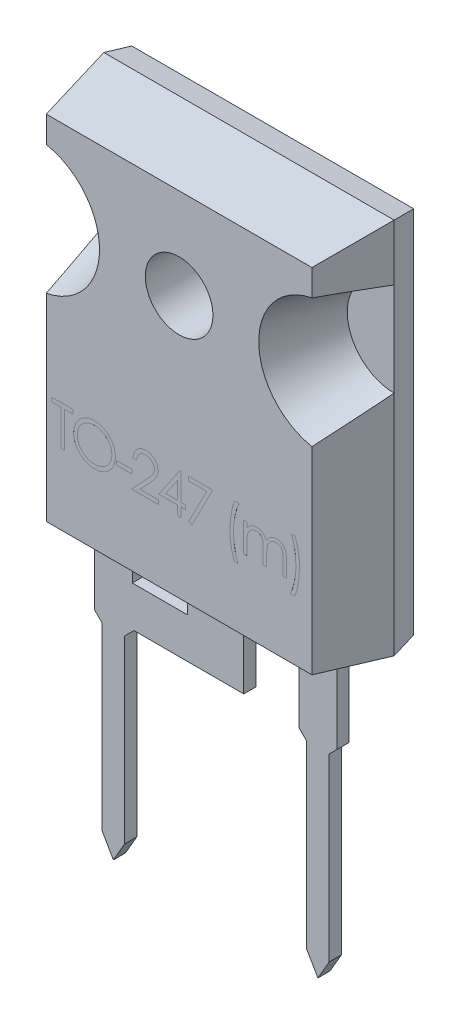
SolidWorks part; units mm, degrees
ref_plane "Front Plane" through (0, 0, 0) normal (0, 0, 1) x (1, 0, 0)
ref_plane "Top Plane" through (0, 0, 0) normal (0, 1, 0) x (1, 0, 0)
ref_plane "Right Plane" through (0, 0, 0) normal (1, 0, 0) x (0, 0, -1)
sketch "Sketch1" plane through (0, 0, 0) normal (0, 0, 1) x (1, 0, 0)
  line L1 (-7.75, 10.075) -> (7.75, 10.075)
  line L2 (-7.75, 10.075) -> (-7.75, -10.075)
  line L3 (-7.75, -10.075) -> (7.75, -10.075)
  line L4 (7.75, 10.075) -> (7.75, -10.075)
  line L5 (-7.75, 10.075) -> (7.75, -10.075) construction
  line L6 (-7.75, -10.075) -> (7.75, 10.075) construction
  point P0 (0, 0)
  dimension "D1" = 15.5
  dimension "D2" = 20.15
extrude "Boss-Extrude1" add sketch "Sketch1" against normal blind 1.27 draft 10 and the other way blind 3.73 draft 10
sketch "Sketch2" plane through (0, 0, 0) normal (0, 0, 1) x (1, 0, 0)
  line L0 (7.75, 10.075) -> (-7.75, 10.075) construction
  line L1 (-5.25, 7.4139) -> (-5.25, 0.8413) construction
  line L2 (-7.75, 10.075) -> (-7.75, -10.075) construction
  line L3 (0, 14.1994) -> (0, -3.2617) construction
  line L4 (7.75, -10.075) -> (7.75, 10.075) construction
  circle A0 centre (0, 4.565) radius 1.805 construction
  circle A1 centre (-7.75, 4.575) radius 2.5
  circle A2 centre (7.75, 4.575) radius 2.5
  dimension "D1" = 5.51
  dimension "D2" = 3.61
  dimension "D3" = 5.5
  dimension "D4" = 5
  dimension "D5" = 2.5
  dimension "D6" = 7.75
extrude "Cut-Extrude1" cut sketch "Sketch2" along normal up to surface (3.73 mm away) draft 15
sketch "Sketch4" plane through (0, 0, 0) normal (0, 0, 1) x (1, 0, 0)
  line L0 (7.75, 10.075) -> (-7.75, 10.075) construction
  circle A0 centre (0, 4.565) radius 1.805
  dimension "D1" = 3.61
  dimension "D2" = 5.51
extrude "Cut-Extrude2" cut sketch "Sketch4" along normal through all both and the other way through all
sketch "Sketch5" plane through (0, 0, 0) normal (0, 1, 0) x (1, 0, 0)
  line L0 (-9.5483, -1.13) -> (8.845, -1.13) construction
  line L1 (7.5261, 1.27) -> (-7.5261, 1.27) construction
  line L2 (0, 2.9425) -> (0, -4.6836) construction
  line L3 (-6.47, -1.13) -> (-4.45, -1.13)
  line L4 (-6.47, -1.13) -> (-6.47, -1.78)
  line L5 (-6.47, -1.78) -> (-4.45, -1.78)
  line L6 (-4.45, -1.13) -> (-4.45, -1.78)
  line L7 (-5.46, -1.13) -> (-5.46, -1.78) construction
  line L8 (6.47, -1.13) -> (6.47, -1.78)
  line L9 (6.47, -1.13) -> (4.45, -1.13)
  line L10 (4.45, -1.13) -> (4.45, -1.78)
  line L11 (6.47, -1.78) -> (4.45, -1.78)
  line L13 (-1.5, -1.13) -> (1.5, -1.13)
  line L14 (-1.5, -1.13) -> (-1.5, -1.78)
  line L15 (-1.5, -1.78) -> (1.5, -1.78)
  line L16 (1.5, -1.13) -> (1.5, -1.78)
  point P21 (0, -1.13)
  dimension "D1" = 2.4
  dimension "D2" = 2.02
  dimension "D3" = 0.65
  dimension "D4" = 5.46
  dimension "D5" = 3
extrude "Boss-Extrude2" add sketch "Sketch5" against normal blind 14.07
sketch "Sketch6" plane through (0, 0, 1.78) normal (0, 0, 1) x (1, 0, 0)
  line L0 (1.5, -14.07) -> (-6.47, -14.07)
  line L1 (-6.47, -14.07) -> (-6.47, -11.9156)
  line L2 (-6.47, -14.07) -> (-6.47, -9.7611) construction
  line L3 (-6.47, -11.9156) -> (1.5, -11.9156)
  line L4 (1.5, -14.07) -> (1.5, -9.7611) construction
  line L5 (1.5, -11.9156) -> (1.5, -14.07)
extrude "Boss-Extrude3" add sketch "Sketch6" against normal up to surface (0.65 mm away) up to face at (-5.46, -11.9729, 1.13)
sketch "Sketch7" plane through (0, 0, -1.27) normal (0, 0, -1) x (-1, 0, 0)
  line L0 (-7.75, 10.075) -> (7.75, 10.075) construction
  line L1 (-5.9, 9.225) -> (5.9, 9.225)
  line L2 (-6.9, 8.225) -> (-6.9, -3.855)
  line L3 (-6.9, -3.855) -> (6.9, -3.855)
  line L4 (6.9, 8.225) -> (6.9, -3.855)
  line L5 (-6.9, 9.225) -> (6.9, -3.855) construction
  line L6 (-6.9, -3.855) -> (6.9, 9.225) construction
  line L7 (7.75, 7.075) -> (7.75, 2.075) construction
  circle A0 centre (0, 4.565) radius 1.805 construction
  circle A1 centre (0, 4.565) radius 1.805
  arc A2 (-6.9, 8.225) -> (-5.9, 9.225) centre (-5.9, 8.225) cw
  arc A3 (6.9, 8.225) -> (5.9, 9.225) centre (5.9, 8.225) ccw
  point P0 (0, 2.685)
  point P5 (0, 0)
  point P6 (0, 0)
  point P8 (0, 0)
  point P9 (0, 0)
  point P10 (0, 0)
  point P11 (0, 0)
  point P12 (0, 0)
  point P13 (0, 2.032)
  dimension "D4" = 1
  dimension "D1" = 13.08
  dimension "D2" = 0.85
  dimension "D3" = 0.85
extrude "Boss-Extrude4" add sketch "Sketch7" along normal blind 0.0001
sketch "Sketch8" plane through (0, 0, 1.78) normal (0, 0, 1) x (1, 0, 0)
  line L0 (-6.06, -14.07) -> (-6.06, -24.1858)
  line L1 (-6.47, -14.07) -> (1.5, -14.07) construction
  line L2 (-6.06, -24.1858) -> (-5.46, -25.225)
  line L3 (-5.46, -25.225) -> (-4.86, -24.1858)
  line L4 (-4.86, -24.1858) -> (-4.86, -14.07)
  line L5 (-7.75, -10.075) -> (7.75, -10.075) construction
  line L6 (-5.46, -9.7611) -> (-5.46, -27.3304) construction
  line L7 (-6.47, -9.7611) -> (-4.45, -9.7611) construction
  line L8 (0, -9.7611) -> (0, -26.1766) construction
  line L9 (-1.5, -9.7611) -> (1.5, -9.7611) construction
  line L10 (-6.06, -14.07) -> (-4.86, -14.07)
  line L11 (6.06, -14.07) -> (6.06, -24.1858)
  line L12 (6.06, -24.1858) -> (5.46, -25.225)
  line L13 (5.46, -25.225) -> (4.86, -24.1858)
  line L14 (4.86, -24.1858) -> (4.86, -14.07)
  line L15 (6.06, -14.07) -> (4.86, -14.07)
  point P9 (-6.06, -24.5365)
  dimension "D1" = 15.15
  dimension "D2" = 1.2
  dimension "D3" = 60
extrude "Boss-Extrude5" add sketch "Sketch8" against normal up to surface (0.65 mm away) up to face at (5.46, -11.9729, 1.13)
chamfer "Chamfer1" distance 0.5 angle 45 4 edges at (4.86, -14.07, 1.455) (6.06, -14.07, 1.455) (-4.86, -14.07, 1.455) (-6.06, -14.07, 1.455)
sketch "Sketch9" plane through (0, 0, 3.73) normal (0, 0, 1) x (1, 0, 0)
  line L0 (-7.0923, -5.6406) -> (7.0923, -5.6406) construction
  line L1 (-7.0923, 1.1379) -> (-7.0923, -9.4173) construction
  line L2 (7.0923, -9.4173) -> (7.0923, 1.1379) construction
  text T0 "TO-247 (m)" font "Century Gothic" height in points 8
extrude "Cut-Extrude3" cut sketch "Sketch9" against normal blind 0.0001
